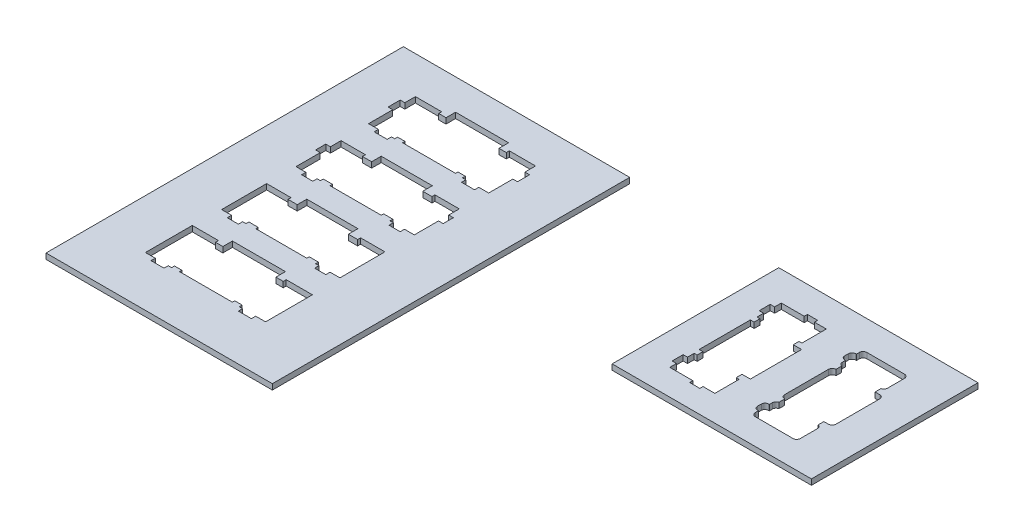
SolidWorks part; units mm, degrees
ref_plane "Front Plane" through (0, 0, 0) normal (0, 0, 1) x (1, 0, 0)
ref_plane "Top Plane" through (0, 0, 0) normal (0, 1, 0) x (1, 0, 0)
ref_plane "Right Plane" through (0, 0, 0) normal (1, 0, 0) x (0, 0, -1)
sketch "Sketch1" plane through (0, 0, 0) normal (0, 1, 0) x (1, 0, 0)
  line L0 (0, 6.985) -> (0, -6.985) construction
  line L1 (6.985, -6.985) -> (-6.985, -6.985)
  line L2 (-6.985, -6.985) -> (-6.985, -6.3246)
  line L3 (-6.985, -6.3246) -> (-9.4996, -6.3246)
  line L4 (-9.4996, -6.3246) -> (-9.4996, -7.112)
  line L5 (-9.4996, -7.112) -> (-10.414, -7.112)
  line L6 (-10.414, -7.112) -> (-10.414, -8.2804)
  line L7 (-10.414, -8.2804) -> (-13.462, -8.2804)
  line L8 (-13.462, -8.2804) -> (-13.462, -7.112)
  line L9 (-13.462, -7.112) -> (-16.1544, -7.112)
  line L10 (-16.1544, -7.112) -> (-16.1544, -0.508)
  line L11 (-16.1544, -0.508) -> (-17.4244, -0.508)
  line L12 (-17.4244, -0.508) -> (-17.4244, 2.286)
  line L13 (-17.4244, 2.286) -> (-16.1544, 2.286)
  line L14 (-16.1544, 2.286) -> (-16.1544, 5.1816)
  line L15 (-16.1544, 5.1816) -> (-9.4996, 5.1816)
  line L16 (-9.4996, 5.1816) -> (-9.4996, 4.3688)
  line L17 (-9.4996, 4.3688) -> (-6.985, 4.3688)
  line L18 (-6.985, 4.3688) -> (-6.985, 6.985)
  line L19 (-6.985, 6.985) -> (6.985, 6.985)
  line L20 (6.985, 4.3688) -> (6.985, 6.985)
  line L21 (9.4996, 4.3688) -> (6.985, 4.3688)
  line L22 (9.4996, 5.1816) -> (9.4996, 4.3688)
  line L23 (16.1544, 5.1816) -> (9.4996, 5.1816)
  line L24 (16.1544, 2.286) -> (16.1544, 5.1816)
  line L25 (17.4244, 2.286) -> (16.1544, 2.286)
  line L26 (17.4244, -0.508) -> (17.4244, 2.286)
  line L27 (16.1544, -0.508) -> (17.4244, -0.508)
  line L28 (16.1544, -7.112) -> (16.1544, -0.508)
  line L29 (13.462, -7.112) -> (16.1544, -7.112)
  line L30 (13.462, -8.2804) -> (13.462, -7.112)
  line L31 (10.414, -8.2804) -> (13.462, -8.2804)
  line L32 (10.414, -7.112) -> (10.414, -8.2804)
  line L33 (9.4996, -7.112) -> (10.414, -7.112)
  line L34 (9.4996, -6.3246) -> (9.4996, -7.112)
  line L35 (6.985, -6.3246) -> (9.4996, -6.3246)
  line L36 (6.985, -6.985) -> (6.985, -6.3246)
  line L37 (-11.938, -8.2804) -> (-11.938, 5.1816) construction
  line L38 (11.938, -8.2804) -> (11.938, 5.1816) construction
  line L44 (0, -13.335) -> (0, -27.305) construction
  line L45 (6.985, -27.305) -> (-6.985, -27.305)
  line L89 (-6.985, -27.305) -> (-6.985, -26.6446)
  line L90 (-6.985, -26.6446) -> (-9.4996, -26.6446)
  line L91 (-9.4996, -26.6446) -> (-9.4996, -27.432)
  line L92 (-9.4996, -27.432) -> (-10.414, -27.432)
  line L105 (-10.414, -27.432) -> (-10.414, -28.6004)
  line L106 (-10.414, -28.6004) -> (-13.462, -28.6004)
  line L107 (-13.462, -28.6004) -> (-13.462, -27.432)
  line L108 (-13.462, -27.432) -> (-16.1544, -27.432)
  line L125 (-16.1544, -27.432) -> (-16.1544, -15.1384)
  line L126 (-16.1544, -15.1384) -> (-9.4996, -15.1384)
  line L127 (-9.4996, -15.1384) -> (-9.4996, -15.9512)
  line L128 (-9.4996, -15.9512) -> (-6.985, -15.9512)
  line L129 (-6.985, -15.9512) -> (-6.985, -13.335)
  line L130 (-6.985, -13.335) -> (6.985, -13.335)
  line L131 (6.985, -15.9512) -> (6.985, -13.335)
  line L132 (9.4996, -15.9512) -> (6.985, -15.9512)
  line L137 (9.4996, -15.1384) -> (9.4996, -15.9512)
  line L138 (16.1544, -15.1384) -> (9.4996, -15.1384)
  line L164 (13.462, -27.432) -> (16.1544, -27.432)
  line L165 (13.462, -28.6004) -> (13.462, -27.432)
  line L166 (10.414, -28.6004) -> (13.462, -28.6004)
  line L167 (10.414, -27.432) -> (10.414, -28.6004)
  line L168 (9.4996, -27.432) -> (10.414, -27.432)
  line L169 (9.4996, -26.6446) -> (9.4996, -27.432)
  line L170 (6.985, -26.6446) -> (9.4996, -26.6446)
  line L171 (6.985, -27.305) -> (6.985, -26.6446)
  line L172 (-11.938, -28.6004) -> (-11.938, -15.1384) construction
  line L173 (11.938, -28.6004) -> (11.938, -15.1384) construction
  line L174 (16.1544, -15.1384) -> (16.1544, -27.432)
  line L175 (0, 27.305) -> (0, 13.335) construction
  line L176 (6.985, 13.335) -> (-6.985, 13.335) construction
  line L177 (-6.985, 13.335) -> (-6.985, 13.9954) construction
  line L178 (-6.985, 13.9954) -> (-9.4996, 13.9954) construction
  line L179 (-9.4996, 13.9954) -> (-9.4996, 13.208) construction
  line L180 (-9.4996, 13.208) -> (-10.414, 13.208) construction
  line L181 (-10.414, 13.208) -> (-10.414, 12.0396) construction
  line L182 (-10.414, 12.0396) -> (-13.462, 12.0396) construction
  line L183 (-13.462, 12.0396) -> (-13.462, 13.208) construction
  line L184 (-13.462, 13.208) -> (-16.1544, 13.208) construction
  line L185 (-16.1544, 13.208) -> (-16.1544, 19.812) construction
  line L186 (-16.1544, 19.812) -> (-17.4244, 19.812) construction
  line L187 (-17.4244, 19.812) -> (-17.4244, 22.606) construction
  line L188 (-17.4244, 22.606) -> (-16.1544, 22.606) construction
  line L189 (-16.1544, 22.606) -> (-16.1544, 25.5016) construction
  line L190 (-16.1544, 25.5016) -> (-9.4996, 25.5016) construction
  line L191 (-9.4996, 25.5016) -> (-9.4996, 24.6888) construction
  line L192 (-9.4996, 24.6888) -> (-6.985, 24.6888) construction
  line L193 (-6.985, 24.6888) -> (-6.985, 27.305) construction
  line L194 (-6.985, 27.305) -> (6.985, 27.305) construction
  line L195 (6.985, 24.6888) -> (6.985, 27.305) construction
  line L196 (9.4996, 24.6888) -> (6.985, 24.6888) construction
  line L197 (9.4996, 25.5016) -> (9.4996, 24.6888) construction
  line L198 (16.1544, 25.5016) -> (9.4996, 25.5016) construction
  line L199 (16.1544, 22.606) -> (16.1544, 25.5016) construction
  line L200 (17.4244, 22.606) -> (16.1544, 22.606) construction
  line L201 (17.4244, 19.812) -> (17.4244, 22.606) construction
  line L202 (16.1544, 19.812) -> (17.4244, 19.812) construction
  line L203 (16.1544, 13.208) -> (16.1544, 19.812) construction
  line L204 (13.462, 13.208) -> (16.1544, 13.208) construction
  line L205 (13.462, 12.0396) -> (13.462, 13.208) construction
  line L206 (10.414, 12.0396) -> (13.462, 12.0396) construction
  line L207 (10.414, 13.208) -> (10.414, 12.0396) construction
  line L208 (9.4996, 13.208) -> (10.414, 13.208) construction
  line L209 (9.4996, 13.9954) -> (9.4996, 13.208) construction
  line L210 (6.985, 13.9954) -> (9.4996, 13.9954) construction
  line L211 (6.985, 13.335) -> (6.985, 13.9954) construction
  line L212 (-11.938, 12.0396) -> (-11.938, 25.5016) construction
  line L213 (11.938, 12.0396) -> (11.938, 25.5016) construction
  line L214 (7.239, 13.081) -> (-7.239, 13.081)
  line L215 (-7.239, 13.081) -> (-7.239, 13.7414)
  line L216 (-7.239, 13.7414) -> (-9.2456, 13.7414)
  line L217 (-9.2456, 13.7414) -> (-9.2456, 12.954)
  line L218 (-9.2456, 12.954) -> (-10.16, 12.954)
  line L219 (-10.16, 12.954) -> (-10.16, 11.7856)
  line L220 (-10.16, 11.7856) -> (-13.716, 11.7856)
  line L221 (-13.716, 11.7856) -> (-13.716, 12.954)
  line L222 (-13.716, 12.954) -> (-16.4084, 12.954)
  line L223 (-16.4084, 12.954) -> (-16.4084, 19.558)
  line L224 (-16.4084, 19.558) -> (-17.6784, 19.558)
  line L225 (-17.6784, 19.558) -> (-17.6784, 22.86)
  line L226 (-17.6784, 22.86) -> (-16.4084, 22.86)
  line L227 (-16.4084, 22.86) -> (-16.4084, 25.7556)
  line L228 (-16.4084, 25.7556) -> (-9.2456, 25.7556)
  line L229 (-9.2456, 25.7556) -> (-9.2456, 24.9428)
  line L230 (-9.2456, 24.9428) -> (-7.239, 24.9428)
  line L231 (-7.239, 24.9428) -> (-7.239, 27.559)
  line L232 (-7.239, 27.559) -> (7.239, 27.559)
  line L233 (7.239, 24.9428) -> (7.239, 27.559)
  line L234 (9.2456, 24.9428) -> (7.239, 24.9428)
  line L235 (9.2456, 25.7556) -> (9.2456, 24.9428)
  line L236 (16.4084, 25.7556) -> (9.2456, 25.7556)
  line L237 (16.4084, 22.86) -> (16.4084, 25.7556)
  line L238 (17.6784, 22.86) -> (16.4084, 22.86)
  line L239 (17.6784, 19.558) -> (17.6784, 22.86)
  line L240 (16.4084, 19.558) -> (17.6784, 19.558)
  line L241 (16.4084, 12.954) -> (16.4084, 19.558)
  line L242 (13.716, 12.954) -> (16.4084, 12.954)
  line L243 (13.716, 11.7856) -> (13.716, 12.954)
  line L244 (10.16, 11.7856) -> (13.716, 11.7856)
  line L245 (10.16, 12.954) -> (10.16, 11.7856)
  line L246 (9.2456, 12.954) -> (10.16, 12.954)
  line L247 (9.2456, 13.7414) -> (9.2456, 12.954)
  line L248 (7.239, 13.7414) -> (9.2456, 13.7414)
  line L249 (7.239, 13.081) -> (7.239, 13.7414)
  line L250 (0, -33.655) -> (0, -47.625) construction
  line L251 (6.985, -47.625) -> (-6.985, -47.625) construction
  line L252 (-6.985, -47.625) -> (-6.985, -46.9646) construction
  line L253 (-6.985, -46.9646) -> (-9.4996, -46.9646) construction
  line L254 (-9.4996, -46.9646) -> (-9.4996, -47.752) construction
  line L255 (-9.4996, -47.752) -> (-10.414, -47.752) construction
  line L256 (-10.414, -47.752) -> (-10.414, -48.9204) construction
  line L257 (-10.414, -48.9204) -> (-13.462, -48.9204) construction
  line L258 (-13.462, -48.9204) -> (-13.462, -47.752) construction
  line L259 (-13.462, -47.752) -> (-16.1544, -47.752) construction
  line L260 (-16.1544, -47.752) -> (-16.1544, -35.4584) construction
  line L261 (-16.1544, -35.4584) -> (-9.4996, -35.4584) construction
  line L262 (-9.4996, -35.4584) -> (-9.4996, -36.2712) construction
  line L263 (-9.4996, -36.2712) -> (-6.985, -36.2712) construction
  line L264 (-6.985, -36.2712) -> (-6.985, -33.655) construction
  line L265 (-6.985, -33.655) -> (6.985, -33.655) construction
  line L266 (6.985, -36.2712) -> (6.985, -33.655) construction
  line L267 (9.4996, -36.2712) -> (6.985, -36.2712) construction
  line L268 (9.4996, -35.4584) -> (9.4996, -36.2712) construction
  line L269 (16.1544, -35.4584) -> (9.4996, -35.4584) construction
  line L270 (13.462, -47.752) -> (16.1544, -47.752) construction
  line L271 (13.462, -48.9204) -> (13.462, -47.752) construction
  line L272 (10.414, -48.9204) -> (13.462, -48.9204) construction
  line L273 (10.414, -47.752) -> (10.414, -48.9204) construction
  line L274 (9.4996, -47.752) -> (10.414, -47.752) construction
  line L275 (9.4996, -46.9646) -> (9.4996, -47.752) construction
  line L276 (6.985, -46.9646) -> (9.4996, -46.9646) construction
  line L277 (6.985, -47.625) -> (6.985, -46.9646) construction
  line L278 (-11.938, -48.9204) -> (-11.938, -35.4584) construction
  line L279 (11.938, -48.9204) -> (11.938, -35.4584) construction
  line L280 (16.1544, -35.4584) -> (16.1544, -47.752) construction
  line L281 (7.239, -47.879) -> (-7.239, -47.879)
  line L282 (-7.239, -47.879) -> (-7.239, -47.2186)
  line L283 (-7.239, -47.2186) -> (-9.2456, -47.2186)
  line L284 (-9.2456, -47.2186) -> (-9.2456, -48.006)
  line L285 (-9.2456, -48.006) -> (-10.16, -48.006)
  line L286 (-10.16, -48.006) -> (-10.16, -49.1744)
  line L287 (-10.16, -49.1744) -> (-13.716, -49.1744)
  line L288 (-13.716, -49.1744) -> (-13.716, -48.006)
  line L289 (-13.716, -48.006) -> (-16.4084, -48.006)
  line L290 (-16.4084, -48.006) -> (-16.4084, -35.2044)
  line L291 (-16.4084, -35.2044) -> (-9.2456, -35.2044)
  line L292 (-9.2456, -35.2044) -> (-9.2456, -36.0172)
  line L293 (-9.2456, -36.0172) -> (-7.239, -36.0172)
  line L294 (-7.239, -36.0172) -> (-7.239, -33.401)
  line L295 (-7.239, -33.401) -> (7.239, -33.401)
  line L296 (7.239, -36.0172) -> (7.239, -33.401)
  line L297 (9.2456, -36.0172) -> (7.239, -36.0172)
  line L298 (9.2456, -35.2044) -> (9.2456, -36.0172)
  line L299 (16.4084, -35.2044) -> (9.2456, -35.2044)
  line L300 (16.4084, -35.2044) -> (16.4084, -48.006)
  line L301 (13.716, -48.006) -> (16.4084, -48.006)
  line L302 (13.716, -49.1744) -> (13.716, -48.006)
  line L303 (10.16, -49.1744) -> (13.716, -49.1744)
  line L304 (10.16, -48.006) -> (10.16, -49.1744)
  line L305 (9.2456, -48.006) -> (10.16, -48.006)
  line L306 (9.2456, -47.2186) -> (9.2456, -48.006)
  line L307 (7.239, -47.2186) -> (9.2456, -47.2186)
  line L308 (7.239, -47.879) -> (7.239, -47.2186)
  line L309 (82.168, 18.6742) -> (82.168, 4.6742)
  line L310 (-29.8725, 35.9279) -> (31.964, 35.9279)
  line L311 (-29.8725, 35.9279) -> (-29.8725, -61.6986)
  line L312 (-29.8725, -61.6986) -> (31.964, -61.6986)
  line L313 (31.964, 35.9279) -> (31.964, -61.6986)
  line L314 (82.168, 4.6742) -> (83.198, 4.6742)
  line L315 (83.198, 4.6742) -> (83.198, 3.0992)
  line L316 (83.198, 3.0992) -> (82.398, 3.0992)
  line L317 (82.398, 3.0992) -> (82.398, 1.2742)
  line L318 (82.398, 1.2742) -> (81.198, 1.2742)
  line L319 (81.198, 1.2742) -> (81.198, -1.7258)
  line L320 (81.198, -1.7258) -> (82.398, -1.7258)
  line L321 (82.398, -1.7258) -> (82.398, -3.5508)
  line L322 (82.398, -3.5508) -> (88.668, -3.5508)
  line L323 (88.668, -3.5508) -> (88.668, -4.4258)
  line L324 (88.668, -4.4258) -> (91.468, -4.4258)
  line L325 (91.468, -4.4258) -> (91.468, -3.5508)
  line L326 (91.468, -3.5508) -> (94.698, -3.5508)
  line L327 (94.698, -3.5508) -> (94.698, 3.0992)
  line L328 (94.698, 3.0992) -> (93.898, 3.0992)
  line L329 (93.898, 3.0992) -> (93.898, 4.6742)
  line L330 (93.898, 4.6742) -> (96.168, 4.6742)
  line L331 (96.168, 4.6742) -> (96.168, 18.6742)
  line L332 (96.168, 11.6742) -> (82.168, 11.6742) construction
  line L333 (93.898, 18.6742) -> (96.168, 18.6742)
  line L334 (93.898, 20.2492) -> (93.898, 18.6742)
  line L335 (94.698, 20.2492) -> (93.898, 20.2492)
  line L336 (94.698, 26.8992) -> (94.698, 20.2492)
  line L337 (91.468, 26.8992) -> (94.698, 26.8992)
  line L338 (91.468, 27.7742) -> (91.468, 26.8992)
  line L339 (88.668, 27.7742) -> (91.468, 27.7742)
  line L340 (88.668, 26.8992) -> (88.668, 27.7742)
  line L341 (82.398, 26.8992) -> (88.668, 26.8992)
  line L342 (82.398, 25.0742) -> (82.398, 26.8992)
  line L343 (81.198, 25.0742) -> (82.398, 25.0742)
  line L344 (81.198, 22.0742) -> (81.198, 25.0742)
  line L345 (82.398, 22.0742) -> (81.198, 22.0742)
  line L346 (82.398, 20.2492) -> (82.398, 22.0742)
  line L347 (83.198, 20.2492) -> (82.398, 20.2492)
  line L348 (83.198, 18.6742) -> (83.198, 20.2492)
  line L349 (82.168, 18.6742) -> (83.198, 18.6742)
  line L350 (89.168, 27.7742) -> (89.168, -4.4258) construction
  line L352 (73.6969, 34.9111) -> (128.1261, 34.9111)
  line L353 (73.6969, 34.9111) -> (73.6969, -10.6029)
  line L354 (73.6969, -10.6029) -> (128.1261, -10.6029)
  line L355 (128.1261, 34.9111) -> (128.1261, -10.6029)
  line L365 (111.0283, -3.5508) -> (111.0283, -4.4258) construction
  line L366 (111.0283, -4.4258) -> (113.8283, -4.4258) construction
  line L367 (113.8283, -4.4258) -> (113.8283, -3.5508) construction
  line L380 (113.8283, 27.7742) -> (113.8283, 26.8992) construction
  line L381 (111.0283, 27.7742) -> (113.8283, 27.7742) construction
  line L382 (111.0283, 26.8992) -> (111.0283, 27.7742) construction
  line L392 (111.5283, 27.7742) -> (111.5283, -4.4258) construction
  point P23 (0, 0)
  point P100 (0, 20.32)
  line B0 (104.5283, 18.6742) -> (104.5283, 4.6742)
  line B1 (104.5283, 4.6742) -> (105.5583, 4.6742)
  line B2 (105.5583, 4.6742) -> (105.5583, 3.0992)
  line B3 (105.5583, 3.0992) -> (104.7583, 3.0992)
  line B4 (104.7583, 3.0992) -> (104.7583, 1.2742)
  line B5 (104.7583, 1.2742) -> (103.5583, 1.2742)
  line B6 (103.5583, 1.2742) -> (103.5583, -1.7258)
  line B7 (103.5583, -1.7258) -> (104.7583, -1.7258)
  line B8 (104.7583, -1.7258) -> (104.7583, -3.5508)
  line B9 (104.7583, -3.5508) -> (111.0283, -3.5508)
  line B10 (113.8283, -3.5508) -> (117.0583, -3.5508)
  line B11 (117.0583, -3.5508) -> (117.0583, 3.0992)
  line B12 (117.0583, 3.0992) -> (116.2583, 3.0992)
  line B13 (116.2583, 3.0992) -> (116.2583, 4.6742)
  line B14 (116.2583, 4.6742) -> (118.5283, 4.6742)
  line B15 (118.5283, 4.6742) -> (118.5283, 18.6742)
  line B16 (118.5283, 11.6742) -> (104.5283, 11.6742) construction
  line B17 (116.2583, 18.6742) -> (118.5283, 18.6742)
  line B18 (116.2583, 20.2492) -> (116.2583, 18.6742)
  line B19 (117.0583, 20.2492) -> (116.2583, 20.2492)
  line B20 (117.0583, 26.8992) -> (117.0583, 20.2492)
  line B21 (113.8283, 26.8992) -> (117.0583, 26.8992)
  line B22 (104.7583, 26.8992) -> (111.0283, 26.8992)
  line B23 (104.7583, 25.0742) -> (104.7583, 26.8992)
  line B24 (103.5583, 25.0742) -> (104.7583, 25.0742)
  line B25 (103.5583, 22.0742) -> (103.5583, 25.0742)
  line B26 (104.7583, 22.0742) -> (103.5583, 22.0742)
  line B27 (104.7583, 20.2492) -> (104.7583, 22.0742)
  line B28 (105.5583, 20.2492) -> (104.7583, 20.2492)
  line B29 (105.5583, 18.6742) -> (105.5583, 20.2492)
  line B30 (104.5283, 18.6742) -> (105.5583, 18.6742)
  line B31 (111.0283, -3.5508) -> (113.8283, -3.5508)
  line B32 (111.0283, 26.8992) -> (113.8283, 26.8992)
  dimension "D1" = 6.6548
  dimension "D2" = 4.2164
  dimension "D3" = 0.8128
  dimension "D4" = 2.794
  dimension "D5" = 0.508
  dimension "D6" = 6.604
  dimension "D7" = 3.048
  dimension "D8" = 13.97
  dimension "D9" = 23.876
  dimension "D10" = 12.2936
  dimension "D11" = 13.462
  dimension "D12" = 0.7874
  dimension "D13" = 1.27
  dimension "D14" = 13.97
  dimension "D15" = 6.6548
  dimension "D29" = 6.35
  dimension "D18" = 0.127
  dimension "D19" = 6.6548
  dimension "D20" = 4.2164
  dimension "D27" = 0.8128
  dimension "D41" = 6.35
  dimension "D53" = 6.35
  dimension "D54" = 13.97
  dimension "D56" = 14
  dimension "D57" = 17.15
  dimension "D58" = 7
  dimension "D59" = 7
  dimension "D60" = 5.53
  dimension "D61" = 4.73
  dimension "D62" = 2.3
  dimension "D63" = 0.5
  dimension "D64" = 5.97
  dimension "D65" = 6.77
  dimension "D66" = 7.97
  dimension "D67" = 20.8
  dimension "D68" = 26.8
  dimension "D69" = 30.45
  dimension "D70" = 32.2
sketch_block_instance "Block1-1"
sketch_block "Block1" parameters "D1"=14, "D2"=17.15, "D3"=20.8, "D4"=26.8, "D5"=30.45, "D6"=1.3355, "D7"=4.6301, "D8"=4.5271, "D9"=14.8079, "D10"=6.6548, "D11"=6.6548, "D12"=2.0393, "D13"=2.794, "D14"=2.794, "D15"=24.7028, "D18"=13.97, "D19"=13.97, "D16"=4.2164, "D17"=0.8128, "D20"=6.604, "D21"=3.048, "D22"=13.97, "D23"=23.876, "D24"=12.2936, "D25"=13.462, "D26"=0.7874, "D27"=1.27, "D28"=13.97, "D29"=13.97, "D30"=2.794, "D31"=0.508, "D32"=6.604, "D33"=3.048, "D34"=13.97, "D35"=23.876, "D36"=12.2936, "D37"=13.462, "D38"=0.7874, "D39"=1.27, "D40"=13.97, "D41"=3.048, "D43"=6.6548, "D44"=4.2164, "D45"=0.8128, "D46"=3.048, "D47"=23.876, "D48"=12.2936, "D49"=13.462, "D50"=0.7874, "D51"=13.97, "D52"=0.127, "D53"=13.97, "D54"=2.6162, "D56"=43.3829, "D57"=3.2285, "D58"=14, "D59"=57.9883, "D60"=57.9883, "D61"=3.235, "D62"=3.235, "D63"=3.7764, "D64"=4.3383, "D65"=10.2844, "D66"=9.8976, "D67"=0.8, "D68"=1.2, "D69"=3.23, "D70"=2.8, "D71"=14, "D72"=17.15, "D73"=7, "D74"=7, "D75"=5.53, "D76"=4.73, "D77"=2.3, "D78"=0.5, "D79"=5.97, "D80"=6.77, "D81"=7.97, "D82"=20.8, "D83"=26.8, "D84"=30.45, "D85"=32.2, "D42"=0.254, "D55"=0.254
extrude "Boss-Extrude1" add sketch "Sketch1" along normal blind 1.524
fillet "Fillet1" radius 1 16 edges at (104.7583, 0.762, -20.2492) (103.5583, 0.762, -22.0742) (103.5583, 0.762, -25.0742) (104.7583, 0.762, -26.8992) (117.0583, 0.762, -20.2492) (117.0583, 0.762, -26.8992) (118.5283, 0.762, -18.6742) (118.5283, 0.762, -4.6742) (117.0583, 0.762, -3.0992) (117.0583, 0.762, 3.5508) (104.7583, 0.762, 3.5508) (103.5583, 0.762, -1.2742) (103.5583, 0.762, 1.7258) (104.7583, 0.762, -3.0992) (104.5283, 0.762, -4.6742) (104.5283, 0.762, -18.6742)
